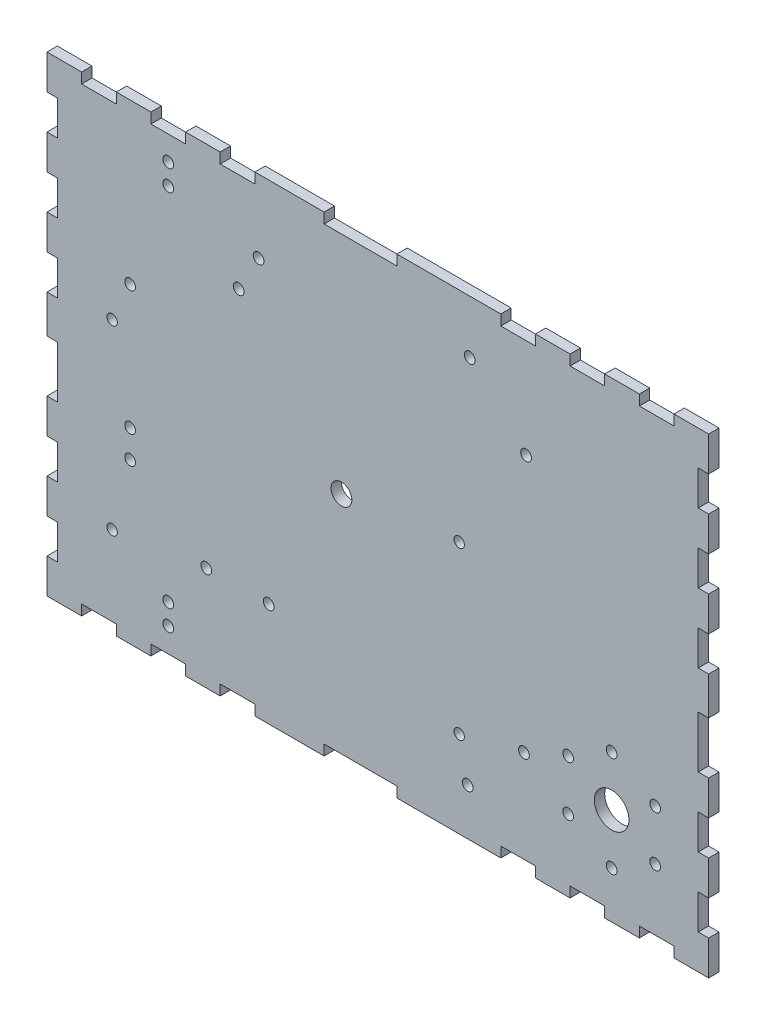
SolidWorks part; units mm, degrees
ref_plane "Front Plane" through (0, 0, 0) normal (0, 0, 1) x (1, 0, 0)
ref_plane "Top Plane" through (0, 0, 0) normal (0, 1, 0) x (1, 0, 0)
ref_plane "Right Plane" through (0, 0, 0) normal (1, 0, 0) x (0, 0, -1)
sketch "Sketch2" plane through (0, 0, 0) normal (0, 0, 1) x (1, 0, 0)
  line L1 (0, 0) -> (191, 0)
  line L2 (0, 0) -> (0, 136)
  line L3 (0, 136) -> (191, 136)
  line L4 (191, 0) -> (191, 136)
  circle A0 centre (35, 16) radius 1.55 construction
  circle A1 centre (35, 10) radius 1.55 construction
  circle A2 centre (24, 46.0692) radius 1.55 construction
  circle A3 centre (24, 54.0692) radius 1.55 construction
  circle A5 centre (24, 89.9308) radius 1.55 construction
  circle A6 centre (35, 120) radius 1.55 construction
  circle A7 centre (35, 126) radius 1.55 construction
  circle A8 centre (175.5574, 35.25) radius 1.55 construction
  circle A9 centre (163, 42.5) radius 1.55 construction
  circle A10 centre (150.4426, 35.25) radius 1.55 construction
  circle A11 centre (150.4426, 20.75) radius 1.55 construction
  circle A12 centre (163, 13.5) radius 1.55 construction
  circle A13 centre (175.5574, 20.75) radius 1.55 construction
  circle A14 centre (35, 16) radius 1.55
  circle A15 centre (35, 10) radius 1.55
  circle A16 centre (24, 46.0692) radius 1.55
  circle A17 centre (24, 54.0692) radius 1.55
  circle A18 centre (18.8, 26) radius 1.5 construction
  circle A19 centre (24, 89.9308) radius 1.55
  circle A20 centre (35, 120) radius 1.55
  circle A21 centre (35, 126) radius 1.55
  circle A22 centre (175.5574, 35.25) radius 1.55
  circle A23 centre (163, 42.5) radius 1.55
  circle A24 centre (150.4426, 35.25) radius 1.55
  circle A25 centre (150.4426, 20.75) radius 1.55
  circle A26 centre (163, 13.5) radius 1.55
  circle A27 centre (175.5574, 20.75) radius 1.55
  circle A28 centre (18.8, 78.5) radius 1.5 construction
  circle A29 centre (18.8, 78.5) radius 1.5
  circle A30 centre (119, 73) radius 1.5 construction
  circle A31 centre (119, 25) radius 1.5 construction
  circle A32 centre (18.8, 26) radius 1.5
  circle A33 centre (119, 73) radius 1.5
  circle A34 centre (119, 25) radius 1.5
extrude "Boss-Extrude1" add sketch "Sketch2" along normal blind 3
ref_axis "Axis1" through (0, 68, 3) along (1, 0, 0)
ref_plane "Plane1" through (0, 68, 0) normal (0, 1, 0) x (1, 0, 0)
ref_axis "Axis2" through (95.5, 0, 3) along (0, 1, 0)
ref_plane "Plane2" through (95.5, 0, 0) normal (1, 0, 0) x (0, 0, -1)
sketch "Sketch3" plane through (0, 0, 3) normal (0, 0, 1) x (1, 0, 0)
  line L0 (0, 3) -> (191, 3) construction
  line L1 (0, 136) -> (0, 0) construction
  line L2 (191, 0) -> (191, 136) construction
  line L3 (0, 0) -> (191, 0) construction
  line L4 (10, 0) -> (10, 3)
  line L5 (20, 0) -> (20, 3)
  line L6 (30, 0) -> (30, 3)
  line L7 (40, 0) -> (40, 3)
  line L8 (50, 0) -> (50, 3)
  line L9 (60, 0) -> (60, 3)
  line L10 (10, 0) -> (20, 0)
  line L11 (20, 3) -> (10, 3)
  line L12 (30, 0) -> (40, 0)
  line L13 (40, 3) -> (30, 3)
  line L14 (50, 0) -> (60, 0)
  line L15 (80, 3) -> (80, 0)
  line L16 (60, 3) -> (50, 3)
  line L17 (181, 0) -> (181, 3)
  line L18 (171, 0) -> (171, 3)
  line L19 (161, 0) -> (161, 3)
  line L20 (151, 0) -> (151, 3)
  line L21 (141, 0) -> (141, 3)
  line L22 (131, 0) -> (131, 3)
  line L23 (181, 0) -> (171, 0)
  line L24 (171, 0) -> (170.9794, -0.0476)
  line L25 (171, 3) -> (181, 3)
  line L26 (181, 3) -> (181.0353, 3.2173)
  line L27 (161, 0) -> (151, 0)
  line L28 (161, 3) -> (151, 3)
  line L29 (141, 0) -> (131, 0)
  line L30 (131, 3) -> (141, 3)
  line L31 (141, 3) -> (140.9859, 2.9583)
  line L32 (101, 0) -> (101, 3)
  line L33 (80, 0) -> (101, 0)
  line L34 (101, 3) -> (80, 3)
  line M15 (0, 0) -> (191, 0)
  dimension "D6" = 20
  dimension "D1" = 3
  dimension "D2" = 10
  dimension "D4" = 10
  dimension "D7" = 30
  dimension "D3" = 6
  dimension "D5" = 6
extrude "Cut-Extrude1" cut sketch "Sketch3" against normal up to next contours L5 L11 L4 M15 | L7 L13 L6 M15 | L9 L16 L8 M15 | L32 L34 L15 M15 | L30 L22 L21 M15 | L19 L28 L20 M15 | L25 L18 L17 M15 region at (176, 1.5, 3) region at (156, 1.5, 3) region at (136, 1.5, 3) region at (90.5, 1.5, 3) region at (55, 1.5, 3) region at (35, 1.5, 3) region at (15, 1.5, 3)
mirror "Mirror1" about plane through (0, 68, 0) normal (0, 1, 0) of "Cut-Extrude1"
sketch "Sketch4" plane through (0, 0, 3) normal (0, 0, 1) x (1, 0, 0)
  line L0 (3, 136) -> (3, 0) construction
  line L1 (10, 136) -> (0, 136) construction
  line L2 (0, 0) -> (10, 0) construction
  line L3 (0, 136) -> (0, 0) construction
  line L4 (0, 126) -> (3, 126)
  line L5 (0, 116) -> (3, 116)
  line L6 (0, 106) -> (3, 106)
  line L7 (0, 96) -> (3, 96)
  line L8 (0, 86) -> (3, 86)
  line L9 (0, 10) -> (3, 10)
  line L10 (0, 20) -> (3, 20)
  line L11 (0, 30) -> (3, 30)
  line L12 (0, 40) -> (3, 40)
  line L13 (0, 50) -> (3, 50)
  line L14 (0, 126) -> (0, 116)
  line L15 (3, 116) -> (3, 126)
  line L16 (0, 106) -> (0, 96)
  line L17 (3, 96) -> (3, 106)
  line L18 (0, 20) -> (0, 10)
  line L19 (3, 10) -> (3, 20)
  line L20 (0, 30) -> (0, 40)
  line L21 (3, 30) -> (3, 40)
  line L22 (0, 65) -> (3, 65)
  line L23 (0, 76) -> (3, 76)
  line L24 (0, 86) -> (0, 76)
  line L25 (3, 76) -> (3, 86)
  line L26 (0, 65) -> (0, 50)
  line L27 (3, 50) -> (3, 65)
  dimension "D1" = 3
  dimension "D2" = 10
  dimension "D4" = 10
  dimension "D6" = 15
  dimension "D3" = 6
  dimension "D5" = 5
extrude "Cut-Extrude2" cut sketch "Sketch4" against normal up to next
mirror "Mirror2" about plane through (95.5, 0, 0) normal (1, 0, 0) of "Cut-Extrude2"
sketch "Sketch6" plane through (0, 0, 3) normal (0, 0, 1) x (1, 0, 0)
  line L0 (116, 0) -> (116, 136) construction
  line L1 (101, 0) -> (131, 0) construction
  line L2 (131, 136) -> (101, 136) construction
  line L3 (191, 68) -> (85, 68) construction
  line L4 (191, 65) -> (191, 76) construction
  dimension "D1" = 106
ref_point "MountPoint-Dif"
sketch "Sketch8" plane through (0, 0, 0) normal (0, 0, -1) x (-1, 0, 0)
  circle A0 centre (-163, 28) radius 8 construction
  circle A1 centre (-163, 28) radius 8
  circle A2 centre (-163, 28) radius 5
  dimension "D1" = 10
extrude "Cut-Extrude3" cut sketch "Sketch8" against normal up to next contours A2 region at (163, 28, 0)
sketch "Sketch9" plane through (0, 0, 3) normal (0, 0, 1) x (1, 0, 0)
  circle A0 centre (85, 68) radius 3
  point P0 (85, 68)
  dimension "D1" = 6
extrude "Cut-Extrude4" cut sketch "Sketch9" against normal up to next
sketch "Sketch10" plane through (0, 0, 3) normal (0, 0, 1) x (1, 0, 0)
  circle A0 centre (61.0861, 114.9893) radius 1.55 construction
  circle A1 centre (55.3425, 104.4531) radius 1.55 construction
  circle A2 centre (138.3021, 104.3671) radius 1.55 construction
  circle A3 centre (122.0386, 120.6305) radius 1.55 construction
  circle A4 centre (64, 30) radius 1.55 construction
  circle A5 centre (46, 30) radius 1.55 construction
  circle A6 centre (137.6988, 29.7288) radius 1.55 construction
  circle A7 centre (121.4354, 13.4653) radius 1.55 construction
  circle A8 centre (61.0861, 114.9893) radius 1.55
  circle A9 centre (55.3425, 104.4531) radius 1.55
  circle A10 centre (138.3021, 104.3671) radius 1.55
  circle A11 centre (122.0386, 120.6305) radius 1.55
  circle A12 centre (64, 30) radius 1.55
  circle A13 centre (46, 30) radius 1.55
  circle A14 centre (137.6988, 29.7288) radius 1.55
  circle A15 centre (121.4354, 13.4653) radius 1.55
extrude "Cut-Extrude5" cut sketch "Sketch10" against normal up to next
